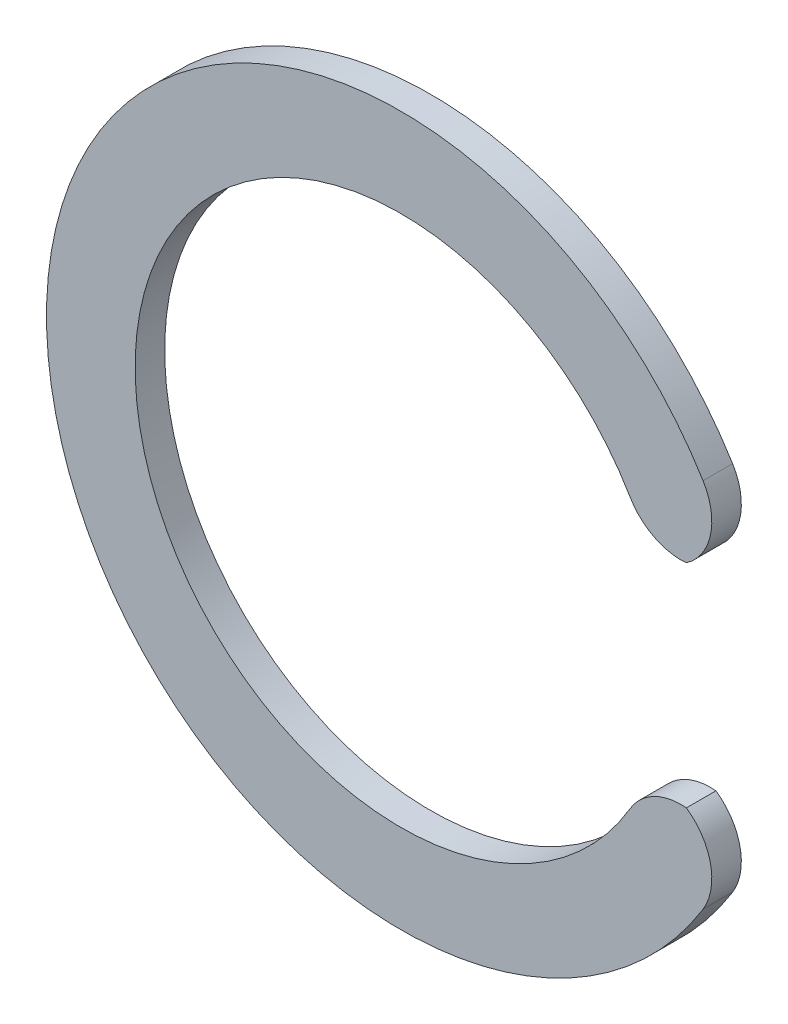
SolidWorks part; units mm, degrees
ref_plane "Front Plane" through (0, 0, 0) normal (0, 0, 1) x (1, 0, 0)
ref_plane "Top Plane" through (0, 0, 0) normal (0, 1, 0) x (1, 0, 0)
ref_plane "Right Plane" through (0, 0, 0) normal (1, 0, 0) x (0, 0, -1)
sketch "Sketch1" plane through (0, 0, 0) normal (0, 0, 1) x (1, 0, 0)
  circle A0 centre (0, 0) radius 4.5
  circle A1 centre (0, 0) radius 6
  dimension "D1" = 9
  dimension "D2" = 12
extrude "Boss-Extrude1" add sketch "Sketch1" along normal blind 0.5
sketch "Sketch2" plane through (0, 0, 0.5) normal (0, 0, 1) x (1, 0, 0)
  line L0 (4.2279, 1.541) -> (5.6372, 2.0547)
  line L1 (4.2279, -1.541) -> (5.6372, -2.0547)
  circle A0 centre (0, 0) radius 4.5 construction
  circle A1 centre (0, 0) radius 6 construction
  circle A3 centre (0, 0) radius 6
  circle A4 centre (0, 0) radius 6
  circle A5 centre (0, 0) radius 4.5
  circle A6 centre (0, 0) radius 4.5
  circle M3 centre (0, 0) radius 6
  circle M4 centre (0, 0) radius 4.5
  dimension "D1" = 0
  dimension "D2" = 0
extrude "Cut-Extrude1" cut sketch "Sketch2" against normal blind 0.5 contours L1 L0 M4 M3 region at (5.1787, 0, 0.5)
fillet "Fillet1" radius 1 4 edges at (4.2279, -1.541, 0.25) (5.6372, -2.0547, 0.25) (4.2279, 1.541, 0.25) (5.6372, 2.0547, 0.25)
